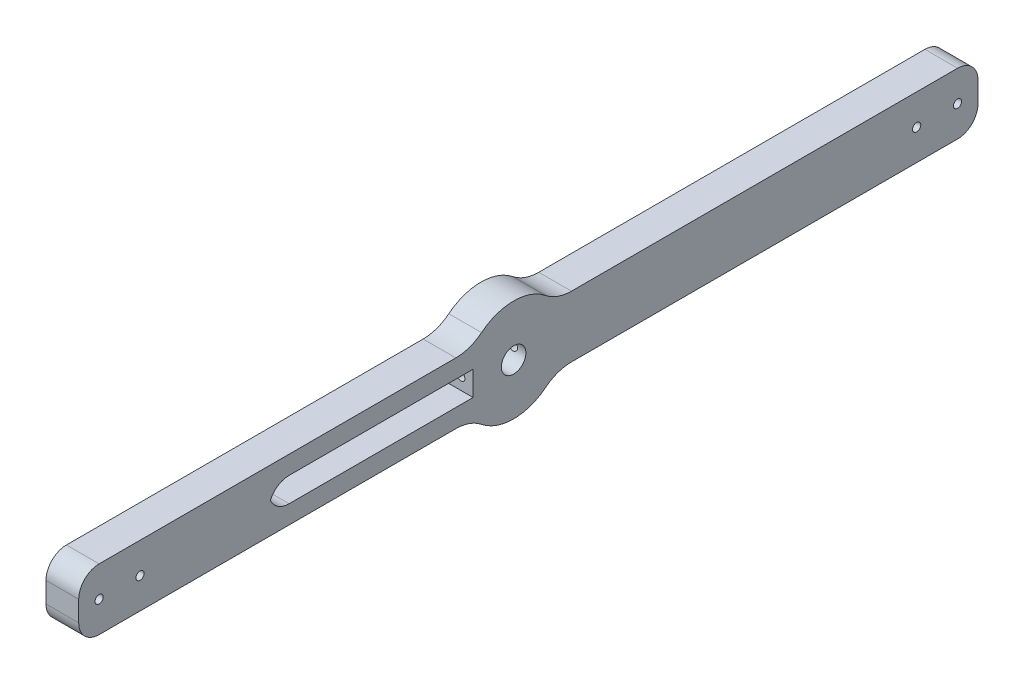
SolidWorks part; units mm, degrees
ref_plane "前视基准面" through (0, 0, 0) normal (0, 0, 1) x (1, 0, 0)
ref_plane "上视基准面" through (0, 0, 0) normal (0, 1, 0) x (1, 0, 0)
ref_plane "右视基准面" through (0, 0, 0) normal (1, 0, 0) x (0, 0, -1)
other "Configuration Table"
sketch "草图1" plane through (0, 0, 0) normal (1, 0, 0) x (0, 0, -1)
  line L1 (0, 0) -> (120, 0)
  line L2 (0, 0) -> (0, 15)
  line L3 (0, 15) -> (120, 15)
  line L4 (120, 0) -> (120, 15)
  dimension "D1" = 15
  dimension "D2" = 120
extrude "凸台-拉伸1" add sketch "草图1" along normal blind 8
fillet "圆角1" radius 5 4 edges at (4, 0, -120) (4, 15, -120) (4, 0, 0) (4, 15, 0)
sketch "草图6" plane through (8, 0, 0) normal (1, 0, 0) x (0, 0, -1)
  circle A0 centre (6.4, 7.5) radius 12.5
extrude "凸台-拉伸2" add sketch "草图6" against normal up to surface (8 mm away) up to face at (0, 7.5, -60)
sketch "草图8" plane through (0, 0, 0) normal (-1, 0, 0) x (0, 0, 1)
  line L0 (-6.4, 12.5) -> (-6.4, 2.5) construction
  circle A0 centre (-6.4, 7.5) radius 3
  dimension "D1" = 6
extrude "切除-拉伸5" cut sketch "草图8" against normal blind 23
sketch "草图9" plane through (0, 0, 0) normal (0, 0, 1) x (1, 0, 0)
  line L0 (0, 20) -> (0, -5) construction
  line L1 (0, 15) -> (8, 15)
  line L2 (0, 15) -> (0, 0)
  line L3 (0, 0) -> (8, 0)
  line L4 (8, 15) -> (8, 0)
  line L5 (2.5, 7.5) -> (0, 7.5) construction
  dimension "D1" = 15
  dimension "D2" = 7.5
  dimension "D3" = 8
extrude "凸台-拉伸3" add sketch "草图9" along normal blind 100
sketch "草图10" plane through (0, 0, 0) normal (-1, 0, 0) x (0, 0, 1)
  line L0 (-6.4, 7.5) -> (29.4071, 7.5) construction
  line L2 (3.523, 10.5) -> (53.523, 10.5)
  line L3 (3.523, 10.5) -> (3.523, 4.5)
  line L4 (3.523, 4.5) -> (53.523, 4.5)
  line L5 (53.523, 10.5) -> (53.523, 4.5)
  dimension "D1" = 6
  dimension "D2" = 3
  dimension "D3" = 50
extrude "切除-拉伸6" cut sketch "草图10" against normal blind 10
sketch "草图4" plane through (0, 0, 0) normal (0, 0, 1) x (1, 0, 0)
  line L1 (8, 0) -> (8, 15) construction
  circle A0 centre (5, 7.5) radius 1
  dimension "D1" = 2
  dimension "D2" = 3
extrude "切除-拉伸7" cut sketch "草图4" against normal blind 15 and the other way blind 7
fillet "圆角2" radius 10 4 edges at (4, 15, -16.4) (4, 0, -16.4) (4, 0, 3.6) (4, 15, 3.6)
fillet "圆角4" radius 5 2 edges at (4, 0, 100) (4, 15, 100)
fillet "圆角5" radius 5 2 edges at (4, 10.5, 53.523) (4, 4.5, 53.523)
sketch "草图11" plane through (0, 0, 0) normal (-1, 0, 0) x (0, 0, 1)
  line L0 (-120, 7.5) -> (-91.0607, 7.5) construction
  line L1 (-120, 5) -> (-120, 10) construction
  line L2 (100, 7.5) -> (83.7402, 7.5) construction
  line L3 (100, 10) -> (100, 5) construction
  circle A0 centre (-115, 7.5) radius 1
  circle A1 centre (-105, 7.5) radius 1
  circle A2 centre (85, 7.5) radius 1
  circle A3 centre (95, 7.5) radius 1
  point P16 (0, 0)
  point P18 (100, 9.0733)
  point P19 (98.7773, 6.6133)
  dimension "D2" = 2
  dimension "D3" = 2
  dimension "D7" = 2
  dimension "D8" = 2
  dimension "D1" = 10
  dimension "D4" = 5
  dimension "D5" = 10
  dimension "D6" = 5
extrude "切除-拉伸8" cut sketch "草图11" against normal blind 10
